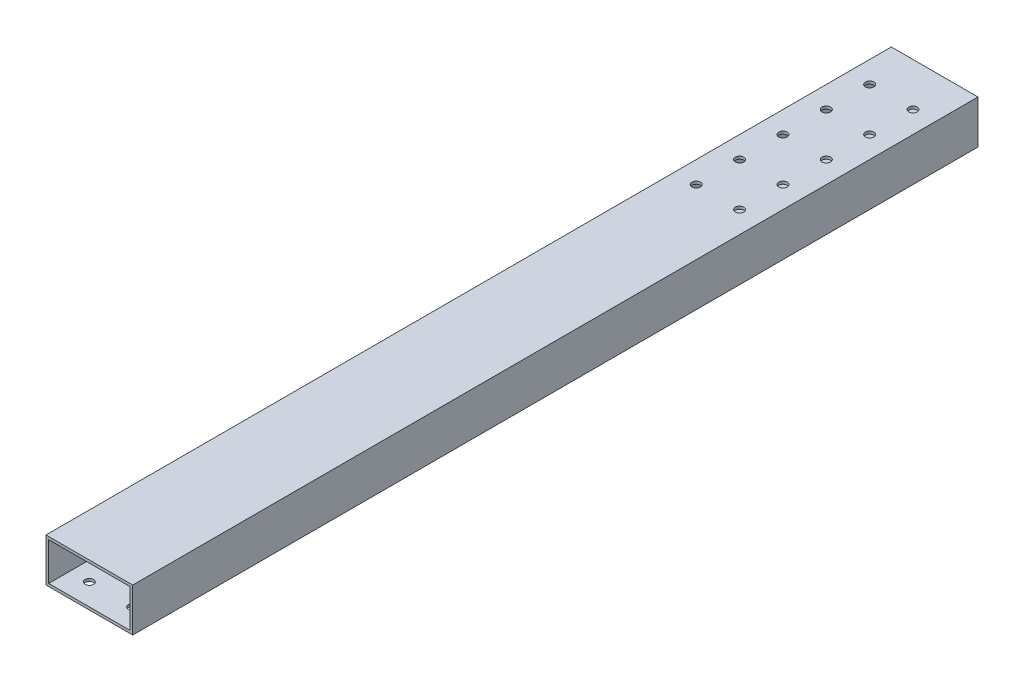
SolidWorks part; units mm, degrees
material "6061-T6 (SS)"
ref_plane "Front Plane" through (0, 0, 0) normal (0, 0, 1) x (1, 0, 0)
ref_plane "Top Plane" through (0, 0, 0) normal (0, 1, 0) x (1, 0, 0)
ref_plane "Right Plane" through (0, 0, 0) normal (1, 0, 0) x (0, 0, -1)
sketch "Sketch1" plane through (0, 0, 0) normal (0, 0, 1) x (1, 0, 0)
  line L1 (-25.4, -12.7) -> (25.4, -12.7)
  line L2 (-25.4, -12.7) -> (-25.4, 12.7)
  line L3 (-25.4, 12.7) -> (25.4, 12.7)
  line L4 (25.4, -12.7) -> (25.4, 12.7)
  line L5 (-25.4, -12.7) -> (25.4, 12.7) construction
  line L6 (-25.4, 12.7) -> (25.4, -12.7) construction
  point P0 (0, 0)
  dimension "D1" = 50.8
  dimension "D2" = 25.4
extrude "Boss-Extrude1" add sketch "Sketch1" along normal blind 495.3 contours L3 L4 L1 L2
shell "Shell1" thickness 1.5875 removed face at (0, 0, 0) removed face at (0, 0, 495.3)
sketch "Sketch2" plane through (0, 12.7, 0) normal (0, 1, 0) x (1, 0, 0)
  line L0 (-25.4, 0) -> (25.4, 0) construction
  circle A0 centre (-12.7, -25.4) radius 2.4892
  circle A1 centre (12.7, -25.4) radius 2.4892
  circle A2 centre (12.7, -50.8) radius 2.4892
  circle A3 centre (12.7, -76.2) radius 2.4892
  circle A4 centre (12.7, -101.6) radius 2.4892
  circle A5 centre (12.7, -127) radius 2.4892
  circle A6 centre (-12.7, -50.8) radius 2.4892
  circle A7 centre (-12.7, -76.2) radius 2.4892
  circle A8 centre (-12.7, -101.6) radius 2.4892
  circle A9 centre (-12.7, -127) radius 2.4892
  dimension "D5" = 4.9784
  dimension "D6" = 12.7
  dimension "D3" = 25.4
  dimension "D4" = 25.4
  dimension "D7" = 25.4
  dimension "D1" = 2
  dimension "D2" = 5
extrude "Cut-Extrude1" cut sketch "Sketch2" against normal up to next
sketch "Sketch3" plane through (0, -12.7, 0) normal (0, -1, 0) x (1, 0, 0)
  line L0 (-25.4, 495.3) -> (-25.4, 0) construction
  line L2 (-25.4, 495.3) -> (25.4, 495.3) construction
  circle A0 centre (-12.7, 457.2) radius 2.4892
  circle A1 centre (12.7, 457.2) radius 2.4892
  circle A2 centre (12.7, 469.9) radius 2.4892
  circle A3 centre (12.7, 482.6) radius 2.4892
  circle A4 centre (-12.7, 469.9) radius 2.4892
  circle A5 centre (-12.7, 482.6) radius 2.4892
  point P16 (-8.912, 24.7066)
  point P17 (-12.7, 31.5546)
  point P18 (0, 0)
  point P19 (10.2626, 12.7)
  dimension "D1" = 4.9784
  dimension "D4" = 12.7
  dimension "D5" = 12.7
  dimension "D6" = 12.7
  dimension "D7" = 25.4
  dimension "D2" = 2
  dimension "D3" = 3
extrude "Cut-Extrude2" cut sketch "Sketch3" against normal up to next
